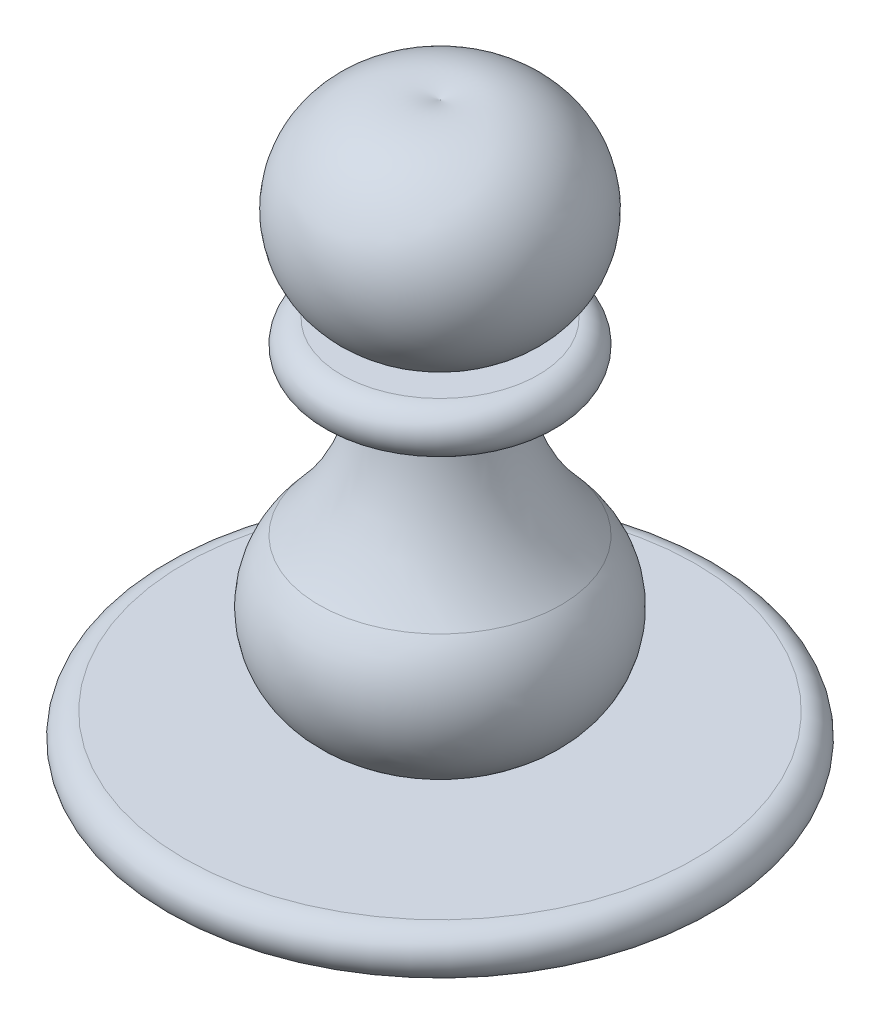
SolidWorks part; units mm, degrees
ref_plane "Front Plane" through (0, 0, 0) normal (0, 0, 1) x (1, 0, 0)
ref_plane "Top Plane" through (0, 0, 0) normal (0, 1, 0) x (1, 0, 0)
ref_plane "Right Plane" through (0, 0, 0) normal (1, 0, 0) x (0, 0, -1)
sketch "Sketch1" plane through (0, 0, 0) normal (0, 0, 1) x (1, 0, 0)
  line L0 (0, -279.9138) -> (0, 13715.7739) construction
  line L1 (-279.9138, 0) -> (13715.7739, 0) construction
sketch "Sketch3" plane through (0, 0, 0) normal (0, 1, 0) x (1, 0, 0)
  circle A0 centre (0, 0) radius 18.3941
extrude "Boss-Extrude3" add sketch "Sketch3" along normal blind 3
fillet "Fillet12" 2 edges at (0, 3, 18.3941) (0, 0, 18.3941) type full round first side face at (0, 3, 18.3941) second side face at (0, 0, 18.3941) middle face at (0, 3, 18.3941)
sketch "Sketch4" plane through (0, 0, 0) normal (0, 0, 1) x (1, 0, 0)
  line L0 (-16.8941, 0) -> (-16.8941, 3) construction
  line L1 (-4, 3) -> (-4, 22.5)
  line L2 (16.8941, 3) -> (-16.8941, 3) construction
  line L3 (-3.6085, 8.9872) -> (-9.6085, 8.9872) construction
  line L4 (-4, 22.5) -> (0, 22.5)
  line L5 (0, -200279.9138) -> (0, 213715.7739) construction
  line L6 (0, 22.5) -> (0, 3)
  line L7 (0, 3) -> (-4, 3)
  arc A0 (-4, 3) -> (-8, 13.0755) centre (-3.6085, 8.9872) cw
  arc A1 (-8, 13.0755) -> (-4, 22.5) centre (-18.9788, 23.2963) ccw
  arc A2 (-16.8941, 3) -> (-16.8941, 0) centre (-16.8941, 1.5) ccw construction
  point P7 (-18.3941, 1.5)
  dimension "D1" = 6
  dimension "D3" = 15
  dimension "D2" = 4
  dimension "D4" = 22.5
  dimension "D5" = 8
revolve "Revolve2" add sketch "Sketch4" angle 360 about L0 region at (-6.185, 9.9669, 0) region at (-2, 12.75, 0)
sketch "Sketch5" plane through (0, 22.5, 0) normal (0, 1, 0) x (1, 0, 0)
  circle A0 centre (0, 0) radius 8
  dimension "D1" = 16
extrude "Boss-Extrude4" add sketch "Sketch5" along normal blind 3
fillet "Fillet13" 2 edges at (-8, 25.5, 0) (-8, 22.5, 0) type full round first side face at (-8, 25.5, 0) second side face at (4, 22.5, 0) middle face at (-8, 25.5, 0)
sketch "Sketch6" plane through (0, 0, 0) normal (0, 0, 1) x (1, 0, 0)
  line L0 (0, 25.5) -> (0, 38)
  line L1 (6.5, 25.5) -> (-6.5, 25.5) construction
  line L2 (0, -200279.9138) -> (0, 213715.7739) construction
  arc A0 (0, 25.5) -> (0, 38) centre (-1.901, 31.75) cw
  dimension "D1" = 12.5
revolve "Revolve3" add sketch "Sketch6" angle 360 about L0
